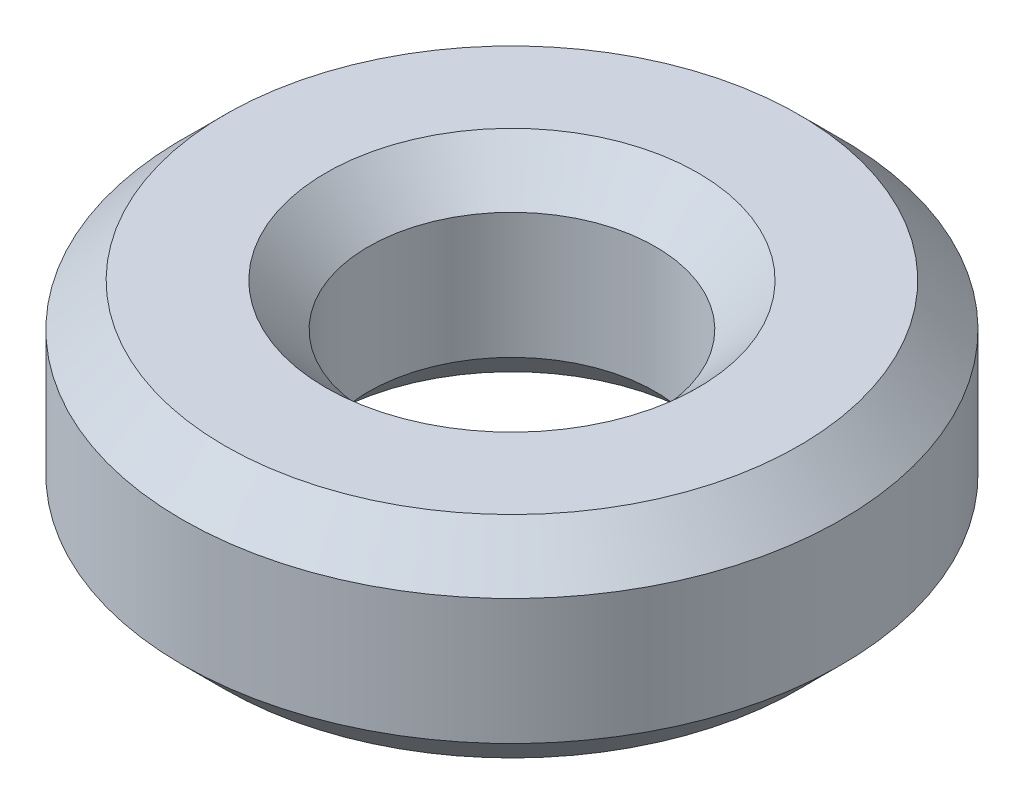
SolidWorks part; units mm, degrees
ref_plane "Front Plane" through (0, 0, 0) normal (0, 0, 1) x (1, 0, 0)
ref_plane "Top Plane" through (0, 0, 0) normal (0, 1, 0) x (1, 0, 0)
ref_plane "Right Plane" through (0, 0, 0) normal (1, 0, 0) x (0, 0, -1)
sketch "Sketch1" plane through (0, 0, 0) normal (0, 1, 0) x (1, 0, 0)
  circle A0 centre (0, 0) radius 20
  dimension "SLEEVE_OD" = 40
extrude "Boss-Extrude1" add sketch "Sketch1" along normal blind 12.7938
sketch "Sketch2" plane through (0, 0, 0) normal (0, 1, 0) x (1, 0, 0)
  circle A0 centre (0, 0) radius 8.7073
  dimension "BORE_D" = 17.4147
extrude "Cut-Extrude1" cut sketch "Sketch2" along normal through all
chamfer "Chamfer1" distance 2.5852 angle 45 4 edges at (0, 12.7938, 8.7073) (0, 0, 8.7073) (0, 0, 20) (0, 12.7938, 20)
